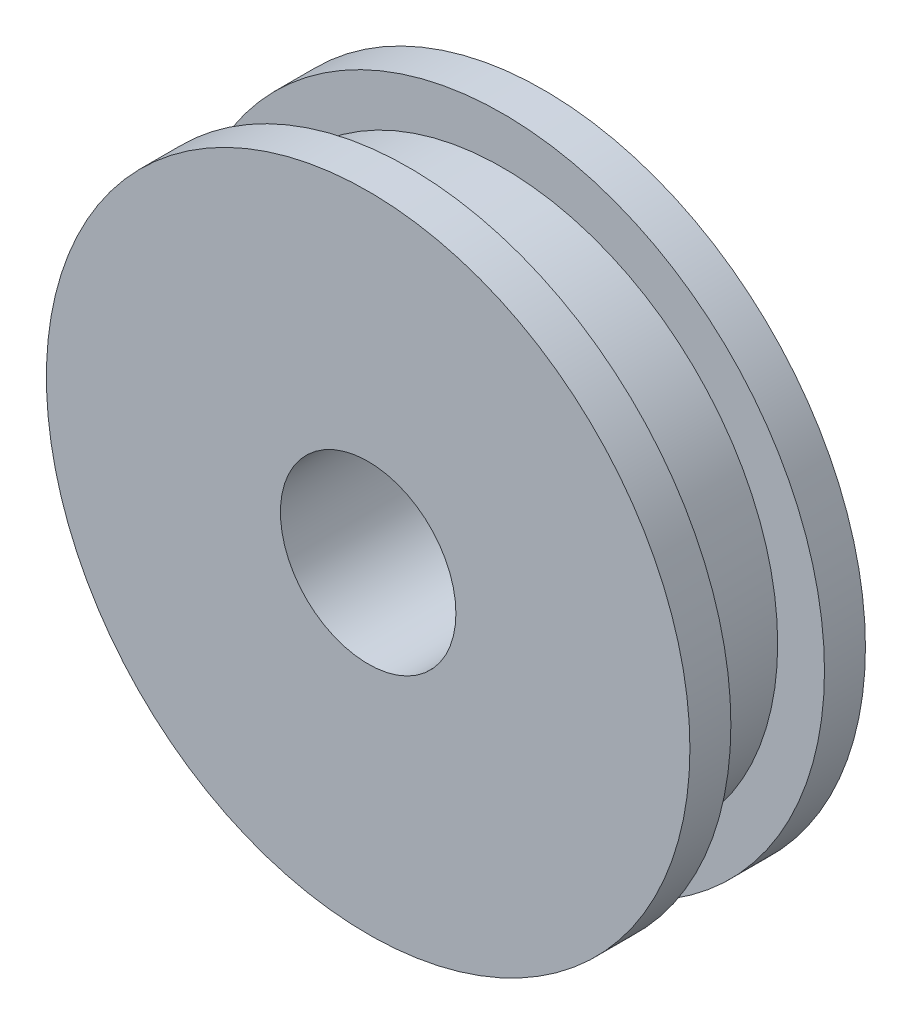
SolidWorks part; units mm, degrees
material "1060-H12"
ref_plane "Plano frontal" through (0, 0, 0) normal (0, 0, 1) x (1, 0, 0)
ref_plane "Plano superior" through (0, 0, 0) normal (0, 1, 0) x (1, 0, 0)
ref_plane "Plano direito" through (0, 0, 0) normal (1, 0, 0) x (0, 0, -1)
sketch "Esboço1" plane through (0, 0, 0) normal (0, 0, 1) x (1, 0, 0)
  circle A0 centre (0, 0) radius 5.5
  dimension "D1" = 11
extrude "Ressalto-extrusão1" add sketch "Esboço1" along normal mid plane 3
sketch "Esboço3" plane through (0, 0, 1.5) normal (0, 0, 1) x (1, 0, 0)
  circle A0 centre (0, 0) radius 1.5
  dimension "D1" = 3
extrude "Corte-extrusão2" cut sketch "Esboço3" against normal through all
sketch "Esboço4" plane through (0, 0, 0) normal (0, 0, 1) x (1, 0, 0)
  point P0 (0, 0)
sketch "Esboço5" plane through (0, 0, 0) normal (0, 1, 0) x (1, 0, 0)
  line L0 (5.5, -0.8) -> (5.5, 0.8)
  line L1 (5.5, -1.5) -> (5.5, 1.5) construction
  line L3 (4.7, -0.8) -> (5.5, -0.8)
  line L4 (0, -1.5) -> (0, 1.5) construction
  line L5 (-5.5, -1.5) -> (5.5, -1.5) construction
  line L6 (5.5, 1.5) -> (-5.5, 1.5) construction
  line L7 (4.7, -0.8) -> (4.7, 0.8)
  line L8 (4.7, 0.8) -> (5.5, 0.8)
  point P5 (5.5, 0)
  dimension "D1" = 1.6
  dimension "D2" = 0.8
revolve "Corte-Revolução1" cut sketch "Esboço5" angle 360 about L4
